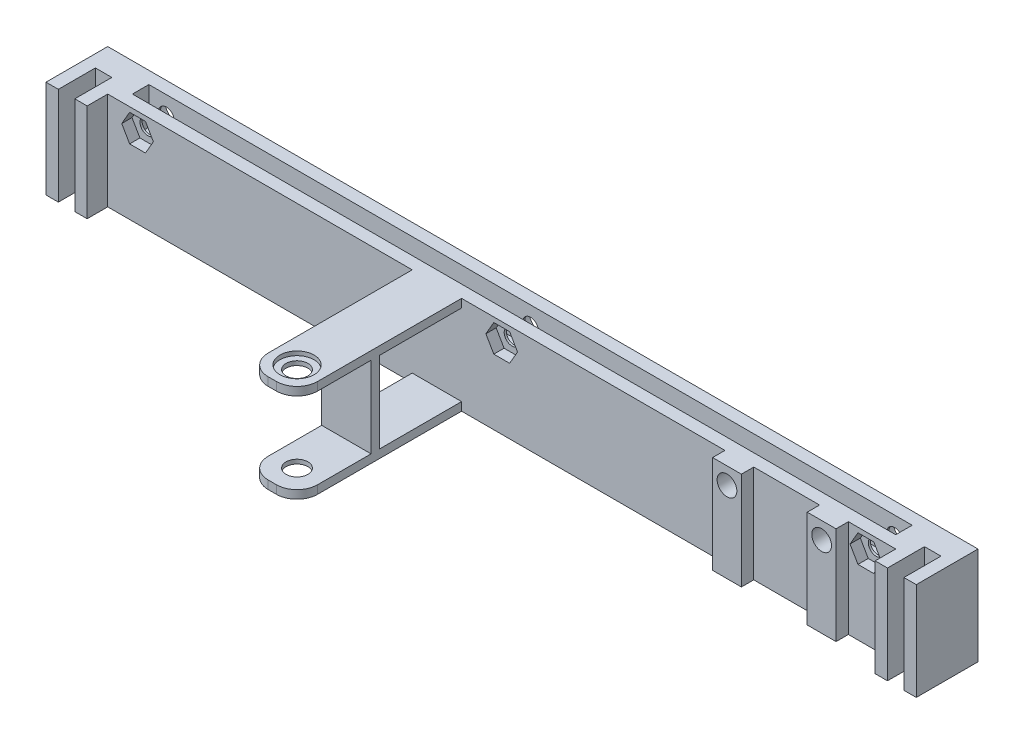
SolidWorks part; units mm, degrees
ref_plane "Front Plane" through (0, 0, 0) normal (1, 0, 0) x (0, 1, 0)
ref_plane "Top Plane" through (0, 0, 0) normal (0, 0, 1) x (0, 1, 0)
ref_plane "Right Plane" through (0, 0, 0) normal (0, 1, 0) x (-1, 0, 0)
sketch "Sketch2" plane through (0, 0, 0) normal (0, 0, 1) x (0, 1, 0)
  line L1 (-71.25, 0) -> (-95, 0)
  line L2 (-71.25, 0) -> (-71.25, 12)
  line L3 (-71.25, 12) -> (-95, 12)
  line L4 (-95, 0) -> (-95, 12)
extrude "Boss-Extrude1" add sketch "Sketch2" along normal blind 10
sketch "Sketch3" plane through (0, 0, 10) normal (0, 0, 1) x (1, 0, 0)
  line L1 (-12, -71.25) -> (0, -71.25)
  line L2 (-12, -71.25) -> (-12, -73.275)
  line L3 (-12, -73.275) -> (0, -73.275)
  line L4 (0, -71.25) -> (0, -73.275)
  line L6 (-12, -73.275) -> (0, -73.275) construction
  dimension "D1" = 2.025
extrude "Boss-Extrude2" add sketch "Sketch3" along normal blind 40
fillet "Fillet1" radius 5 2 edges at (0, -72.2625, 50) (-12, -72.2625, 50)
ref_plane "Plane1" through (0, -83.125, 0) normal (0, 1, 0) x (1, 0, 0)
mirror "Mirror1" about plane through (0, -83.125, 0) normal (0, 1, 0) of "Fillet1", "Boss-Extrude2"
sketch "Sketch5" plane through (0, -95, 0) normal (0, -1, 0) x (1, 0, 0)
  line L1 (-6, 50) -> (-12, 50)
  line L2 (-6, 50) -> (-6, 44)
  line L3 (-6, 44) -> (-12, 44)
  line L4 (-12, 50) -> (-12, 44)
  line L5 (-5, 50) -> (-7, 50) construction
  line L6 (-12, 45) -> (-12, 0) construction
  circle A0 centre (-6, 44) radius 2.65
  dimension "D1" = 6
extrude "Cut-Extrude1" cut sketch "Sketch5" against normal through all contours A0
sketch "Sketch6" plane through (0, -95, 0) normal (0, -1, 0) x (1, 0, 0)
  line L1 (-6, 50) -> (-12, 50)
  line L2 (-6, 50) -> (-6, 44)
  line L3 (-6, 44) -> (-12, 44)
  line L4 (-12, 50) -> (-12, 44)
  line L6 (-5, 50) -> (-7, 50) construction
  line L7 (-12, 45) -> (-12, 0) construction
  circle A0 centre (-6, 44) radius 4.15
  dimension "D1" = 6
extrude "Cut-Extrude2" cut sketch "Sketch6" against normal blind 1 contours A0
mirror "Mirror2" about plane through (0, -83.125, 0) normal (0, 1, 0) of "Cut-Extrude2"
sketch "Sketch7" plane through (0, 0, 0) normal (0, 0, -1) x (1, 0, 0)
  line L1 (-6, 95) -> (-96, 95)
  line L2 (-6, 95) -> (-6, 71.25)
  line L3 (-6, 71.25) -> (-96, 71.25)
  line L4 (-96, 95) -> (-96, 71.25)
  line L5 (-6, 95) -> (115.5, 95)
  line L6 (-6, 95) -> (-6, 71.25)
  line L7 (-6, 71.25) -> (115.5, 71.25)
  line L8 (115.5, 95) -> (115.5, 71.25)
  line L10 (-12, 95) -> (0, 95) construction
  line L11 (0, 71.25) -> (-12, 71.25) construction
  line M20 (0, 71.25) -> (0, 95)
  line M22 (-12, 95) -> (-12, 71.25)
  dimension "D1" = 90
  dimension "D2" = 121.5
extrude "Boss-Extrude3" add sketch "Sketch7" against normal blind 10 contours L1 L4 L3 M22 | L8 L5 L7 M20 region at (-54, -83.125, 0) region at (57.75, -83.125, 0)
sketch "Sketch8" plane through (0, 0, 10) normal (0, 0, 1) x (1, 0, 0)
  line L1 (115.5, -71.25) -> (105.5, -71.25)
  line L2 (115.5, -71.25) -> (115.5, -95)
  line L3 (115.5, -95) -> (105.5, -95)
  line L4 (105.5, -71.25) -> (105.5, -95)
  line L6 (-96, -71.25) -> (-86, -71.25)
  line L7 (-96, -71.25) -> (-96, -95)
  line L8 (-96, -95) -> (-86, -95)
  line L9 (-86, -71.25) -> (-86, -95)
  dimension "D1" = 10
  dimension "D2" = 10
extrude "Boss-Extrude4" add sketch "Sketch8" along normal blind 5
sketch "Sketch10" plane through (-12, 0, 0) normal (-1, 0, 0) x (0, -1, 0)
  line L0 (95, 45) -> (95, 10) construction
  line L1 (71.25, 10) -> (95, 10)
  line L2 (71.25, 10) -> (71.25, 12)
  line L3 (71.25, 12) -> (95, 12)
  line L4 (95, 10) -> (95, 12)
  dimension "D1" = 2
extrude "Boss-Extrude5" [suppressed] add sketch "Sketch10" along normal blind 24
sketch "Sketch18" plane through (0, -92.975, 0) normal (0, 1, 0) x (-1, 0, 0)
  line L0 (12, 45) -> (12, 10) construction
  line L1 (0, 10) -> (12, 10)
  line L2 (0, 10) -> (0, 30)
  line L3 (0, 30) -> (12, 30)
  line L4 (12, 10) -> (12, 30)
  line L6 (0, 30) -> (12, 30)
  line L7 (0, 30) -> (0, 32)
  line L8 (0, 32) -> (12, 32)
  line L9 (12, 30) -> (12, 32)
  dimension "D1" = 20
  dimension "D2" = 2
extrude "Boss-Extrude7" add sketch "Sketch18" along normal up to next contours L7 L6 L9 L8
sketch "Sketch11" plane through (0, -71.25, 0) normal (0, 1, 0) x (-1, 0, 0)
  line L1 (86, 0) -> (-105.5, 0)
  line L2 (86, 0) -> (86, 10)
  line L3 (86, 10) -> (-105.5, 10)
  line L4 (-105.5, 0) -> (-105.5, 10)
  line L5 (83, 7) -> (-102.5, 7)
  line L6 (-102.5, 3) -> (-102.5, 7)
  line L7 (83, 3) -> (-102.5, 3)
  line L8 (83, 3) -> (83, 7)
  line L12 (96, 0) -> (86, 0)
  line L13 (96, 0) -> (96, 10)
  line L14 (96, 10) -> (86, 10)
  line L15 (86, 0) -> (86, 10)
extrude "Cut-Extrude3" cut sketch "Sketch11" against normal blind 9 contours L7 L8 L5 L6 region at (9.75, -71.25, 5)
mirror "Mirror3" about plane through (0, -83.125, 0) normal (0, 1, 0) of "Cut-Extrude3"
sketch "Sketch12" plane through (0, 0, 10) normal (0, 0, 1) x (1, 0, 0)
  line L1 (-86, -71.25) -> (-78.75, -71.25)
  line L2 (-86, -71.25) -> (-86, -75.75)
  line L3 (-86, -75.75) -> (-78.75, -75.75)
  line L4 (-78.75, -71.25) -> (-78.75, -75.75)
  circle A0 centre (-78.75, -75.75) radius 1.9
  circle A1 centre (-78.75, -75.75) radius 3.15
  dimension "D3" = 3.8
  dimension "D4" = 6.3
  dimension "D1" = 7.25
  dimension "D2" = 4.5
extrude "Cut-Extrude4" cut sketch "Sketch12" against normal through all and the other way through all contours A0
sketch "Sketch15" plane through (0, 0, 0) normal (0, 0, 1) x (1, 0, 0)
  circle A0 centre (-78.75, -75.75) radius 3.35
  dimension "D1" = 6.7
extrude "Cut-Extrude5" cut sketch "Sketch15" along normal blind 2.5
sketch "Sketch16" plane through (0, 0, 10) normal (0, 0, 1) x (1, 0, 0)
  line L0 (-82.5964, -75.75) -> (-80.6732, -79.0811)
  line L1 (-82.25, -75.75) -> (-80.5, -78.7811)
  line L2 (-80.5, -78.7811) -> (-77, -78.7811)
  line L3 (-77, -78.7811) -> (-75.25, -75.75)
  line L4 (-75.25, -75.75) -> (-77, -72.7189)
  line L5 (-77, -72.7189) -> (-80.5, -72.7189)
  line L6 (-80.5, -72.7189) -> (-82.25, -75.75)
  line L7 (-80.6732, -79.0811) -> (-76.8268, -79.0811)
  line L8 (-76.8268, -79.0811) -> (-74.9036, -75.75)
  line L9 (-74.9036, -75.75) -> (-76.8268, -72.4189)
  line L10 (-76.8268, -72.4189) -> (-80.6732, -72.4189)
  line L11 (-80.6732, -72.4189) -> (-82.5964, -75.75)
  circle A0 centre (-78.75, -75.75) radius 3.0311 construction
  circle M23 centre (-78.75, -75.75) radius 1.9
extrude "Cut-Extrude6" cut sketch "Sketch16" against normal blind 2.5 contours L10 L11 L0 L7 L8 L9 L6 L5 L4 L3 L2 L1 | L5 L6 L1 L2 L3 L4 M23 region at (-81.5467, -74.1353, 10) region at (-81.2948, -74.2808, 10)
pattern_linear "LPattern1" count 3 spacing 88.5 along (1, 0, 0) of "Cut-Extrude4", "Cut-Extrude6", "Cut-Extrude5"
sketch "Sketch14" plane through (0, 0, 10) normal (0, 0, 1) x (1, 0, 0)
  line L0 (0, -95) -> (105.5, -95) construction
  line L1 (105.5, -71.25) -> (94, -71.25)
  line L2 (105.5, -71.25) -> (105.5, -95)
  line L3 (105.5, -95) -> (94, -95)
  line L4 (94, -71.25) -> (94, -95)
  line L6 (94, -71.25) -> (87, -71.25)
  line L7 (94, -71.25) -> (94, -95)
  line L8 (94, -95) -> (87, -95)
  line L9 (87, -71.25) -> (87, -95)
  line L10 (87, -71.25) -> (71, -71.25)
  line L11 (87, -71.25) -> (87, -95)
  line L12 (87, -95) -> (71, -95)
  line L13 (71, -71.25) -> (71, -95)
  line L14 (71, -71.25) -> (64, -71.25)
  line L15 (71, -71.25) -> (71, -95)
  line L16 (71, -95) -> (64, -95)
  line L17 (64, -71.25) -> (64, -95)
  line M22 (105.5, -71.25) -> (0, -71.25)
  line M24 (0, -95) -> (105.5, -95)
  dimension "D1" = 11.5
  dimension "D2" = 7
  dimension "D3" = 16
  dimension "D4" = 7
extrude "Boss-Extrude6" add sketch "Sketch14" along normal blind 3 contours L17 L13 M22 M24 | L9 L4 M22 M24 region at (90.5, -83.125, 10) region at (67.5, -83.125, 10)
sketch "Sketch19" plane through (0, -83.125, 0) normal (0, 1, 0) x (1, 0, 0)
  line L1 (0, -10) -> (40, -10)
  line L2 (0, -10) -> (0, -37)
  line L3 (0, -37) -> (40, -37)
  line L4 (40, -10) -> (40, -37)
  dimension "D1" = 27
  dimension "D2" = 40
extrude "Boss-Extrude8" [suppressed] add sketch "Sketch19" against normal blind 1 and the other way blind 1
sketch "Sketch21" plane through (0, -71.25, 0) normal (0, 1, 0) x (-1, 0, 0)
  line L0 (-112.5, 6) -> (-108.5, 6)
  line L1 (-115.5, 15) -> (-112.5, 15)
  line L2 (-115.5, 15) -> (-115.5, 6)
  line L3 (-115.5, 6) -> (-112.5, 6)
  line L4 (-112.5, 15) -> (-112.5, 6)
  line L5 (-105.5, 15) -> (-108.5, 15)
  line L6 (-105.5, 15) -> (-105.5, 6)
  line L7 (-105.5, 6) -> (-108.5, 6)
  line L8 (-108.5, 15) -> (-108.5, 6)
  line M22 (-105.5, 15) -> (-115.5, 15)
  dimension "D2" = 3
  dimension "D4" = 9
extrude "Cut-Extrude7" cut sketch "Sketch21" against normal up to next contours L8 L4 L0 M22 region at (110.5, -71.25, 10.5)
pattern_linear "LPattern2" count 2 spacing 201.5 along (-1, 0, 0) of "Cut-Extrude7"
sketch "Sketch22" plane through (0, 0, 13) normal (0, 0, 1) x (1, 0, 0)
  line L1 (94, -71.25) -> (90.5, -71.25)
  line L2 (94, -71.25) -> (94, -75.37)
  line L3 (94, -75.37) -> (90.5, -75.37)
  line L4 (90.5, -71.25) -> (90.5, -75.37)
  circle A0 centre (90.5, -75.37) radius 2.4
  dimension "D1" = 4.12
extrude "Cut-Extrude8" cut sketch "Sketch22" against normal blind 3.8 contours A0
pattern_linear "LPattern3" count 2 spacing 23 along (-1, 0, 0) of "Cut-Extrude8"
equation "\"whitekey_cutout_length\"= 101.5"
equation "\"wall_thickness\"=10"
equation "\"base_mount_height\"=40"
equation "\"D1@Boss-Extrude2\"=\"base_mount_height\""
equation "\"D1@Sketch7\"=\"base_rear_length\"+\"wall_thickness\""
equation "\"D2@Sketch7\"=\"wall_thickness\"+\"base_front_length\""
equation "\"base_rear_length\"=80"
equation "\"D1@Boss-Extrude3\"=\"wall_thickness\""
equation "\"D1@Sketch8\"=\"wall_thickness\""
equation "\"D2@Sketch8\"=\"wall_thickness\""
equation "\"dowel_recess_offset\"=3"
equation "\"D1@Sketch11\"=\"dowel_recess_offset\""
equation "\"dowel_recess_depth\"=9"
equation "\"D1@Cut-Extrude3\"=\"dowel_recess_depth\""
equation "\"guide_brace_height\"=20"
equation "\"D1@Sketch18\"=\"guide_brace_height\""
equation "\"guide_brace_thickness\"=2"
equation "\"D2@Sketch18\"=\"guide_brace_thickness\""
equation "\"D3@LPattern1\"=0.5*(\"base_front_length\"+\"base_rear_length\"-\"screw_hole_wall_offset\"*2)"
equation "\"base_front_length\"=111.5"
equation "\"screw_hole_wall_offset\"=7.25"
equation "\"screw_hole_edge_inset\"=4.5"
equation "\"D1@Sketch12\"=\"screw_hole_wall_offset\""
equation "\"D2@Sketch12\"=\"screw_hole_edge_inset\""
equation "\"screw_hole_diameter\"=3.8"
equation "\"screw_head_hole_diameter\"=6.7"
equation "\"screw_nut_hole_side_len\"=3.5"
equation "\"D3@Sketch12\"=\"screw_hole_diameter\""
equation "\"D1@Sketch15\"=\"screw_head_hole_diameter\""
equation "\"D1@Sketch16\"=\"screw_nut_hole_side_len\""
equation "\"D1@Boss-Extrude6\"=6-\"dowel_recess_offset\""
equation "\"D1@Sketch21\"=\"dowel_recess_depth\""
equation "\"D2@Sketch21\"=\"dowel_recess_offset\""
equation "\"D3@Sketch21\"=\"dowel_recess_offset\""
equation "\"D4@Sketch21\"=\"dowel_recess_depth\""
equation "\"D3@LPattern2\"=\"base_front_length\"+\"base_rear_length\"+\"wall_thickness\""
equation "\"key_mount_recess_length\"=50"
equation "\"key_mount_recess_height\"=12.5"
equation "\"key_mount_recess_depth\"=1.5"
equation "\"screw_shaft_diameter\"=3.5"
equation "\"switch_board_width\"=30"
equation "\"D2@Sketch14\"=\"screw_shaft_diameter\"*2"
equation "\"D4@Sketch14\"=\"screw_shaft_diameter\"*2"
equation "\"D3@Sketch14\"=\"switch_board_width\"-\"screw_shaft_diameter\"*4"
equation "\"heatset_insert_hole_diameter\"=4.8"
equation "\"heatset_insert_hole_depth\"=3.8"
equation "\"D2@Sketch22\"=\"heatset_insert_hole_diameter\""
equation "\"D1@Cut-Extrude8\"=\"heatset_insert_hole_depth\""
equation "\"D3@LPattern3\"=\"switch_board_width\"-\"screw_shaft_diameter\"*2"
